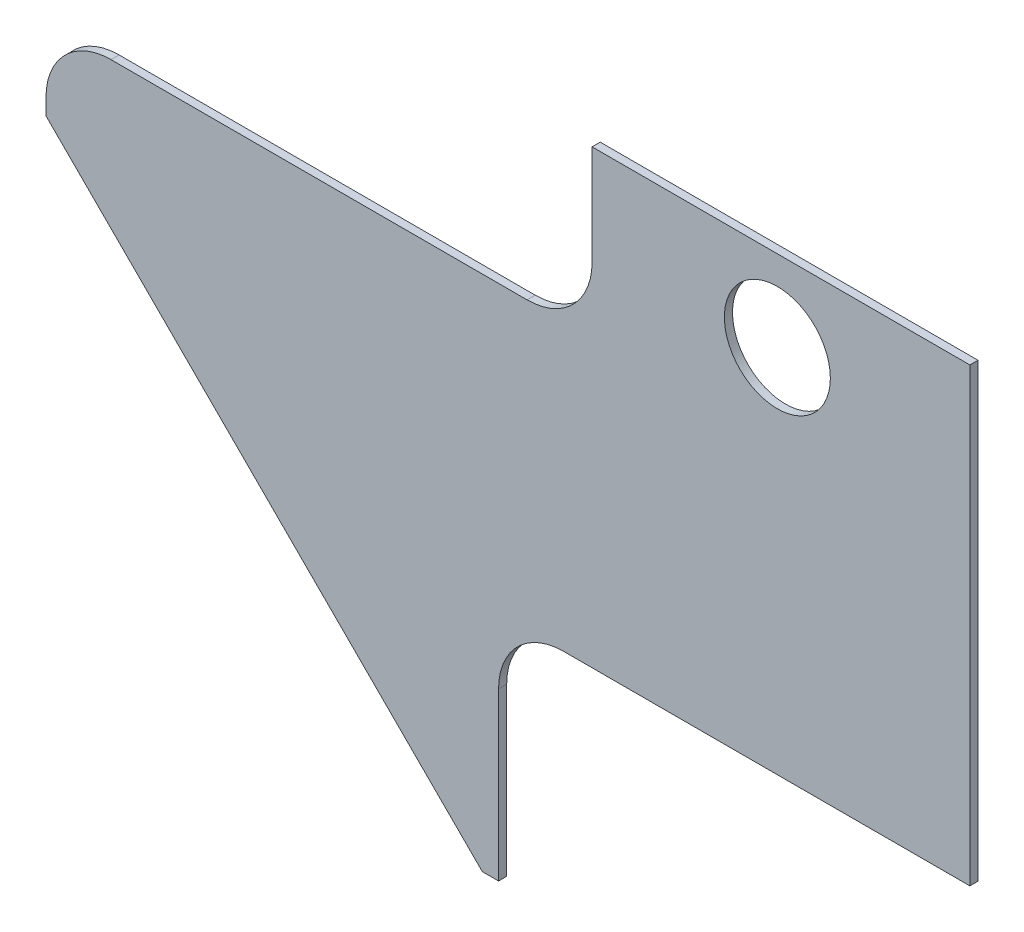
SolidWorks part; units mm, degrees
ref_plane "Front Plane" through (0, 0, 0) normal (0, 0, 1) x (1, 0, 0)
ref_plane "Top Plane" through (0, 0, 0) normal (0, 1, 0) x (1, 0, 0)
ref_plane "Right Plane" through (0, 0, 0) normal (1, 0, 0) x (0, 0, -1)
sketch "Sketch1" plane through (0, 0, 0) normal (0, 0, 1) x (1, 0, 0)
  line L0 (-138.2594, 48.9915) -> (32.2106, -121.4785)
  line L1 (32.2106, -121.4785) -> (222.7106, -121.4785)
  line L2 (-138.2594, 145.2215) -> (-138.2594, 48.9915)
  line L3 (-138.2594, 145.2215) -> (222.7106, 145.2215)
  line L4 (222.7106, -121.4785) -> (222.7106, 145.2215)
  circle A0 centre (147.4906, 113.4715) radius 20.701
  circle A2 centre (147.4906, 113.4715) radius 69.85 construction
  circle A3 centre (147.4906, 113.4715) radius 285.75 construction
  point P0 (0, 0)
  point P2 (147.4906, 113.4715)
  dimension "D4" = 234.95
  dimension "D1" = 45
  dimension "D2" = 266.7
  dimension "D5" = 247.65
extrude "Boss-Extrude1" add sketch "Sketch1" along normal blind 3.175
sketch "Sketch2" plane through (0, 0, 3.175) normal (0, 0, 1) x (1, 0, 0)
  line L0 (32.2106, -121.4785) -> (222.7106, -121.4785) construction
  line L1 (222.7106, -121.4785) -> (38.5606, -121.4785)
  line L2 (222.7106, -121.4785) -> (222.7106, -31.0571)
  line L3 (222.7106, -31.0571) -> (38.5606, -31.0571)
  line L4 (38.5606, -121.4785) -> (38.5606, -31.0571)
extrude "Cut-Extrude1" cut sketch "Sketch2" against normal through all contours L3 L4 L1 L2
fillet "Fillet1" radius 25.4 1 edges at (38.5606, -31.0571, 1.5875)
sketch "Sketch4" plane through (0, 0, 3.175) normal (0, 0, 1) x (1, 0, 0)
  line L1 (-138.2594, 145.2215) -> (-138.2594, 48.9915) construction
  line L3 (-138.2594, 145.2215) -> (75.1006, 145.2215)
  line L4 (-138.2594, 145.2215) -> (-138.2594, 80.7415)
  line L5 (-138.2594, 80.7415) -> (75.1006, 80.7415)
  line L6 (75.1006, 145.2215) -> (75.1006, 80.7415)
extrude "Cut-Extrude2" cut sketch "Sketch4" against normal through all contours L5 L6 L3 L4
fillet "Fillet2" radius 25.4 2 edges at (-138.2594, 80.7415, 1.5875) (75.1006, 80.7415, 1.5875)
